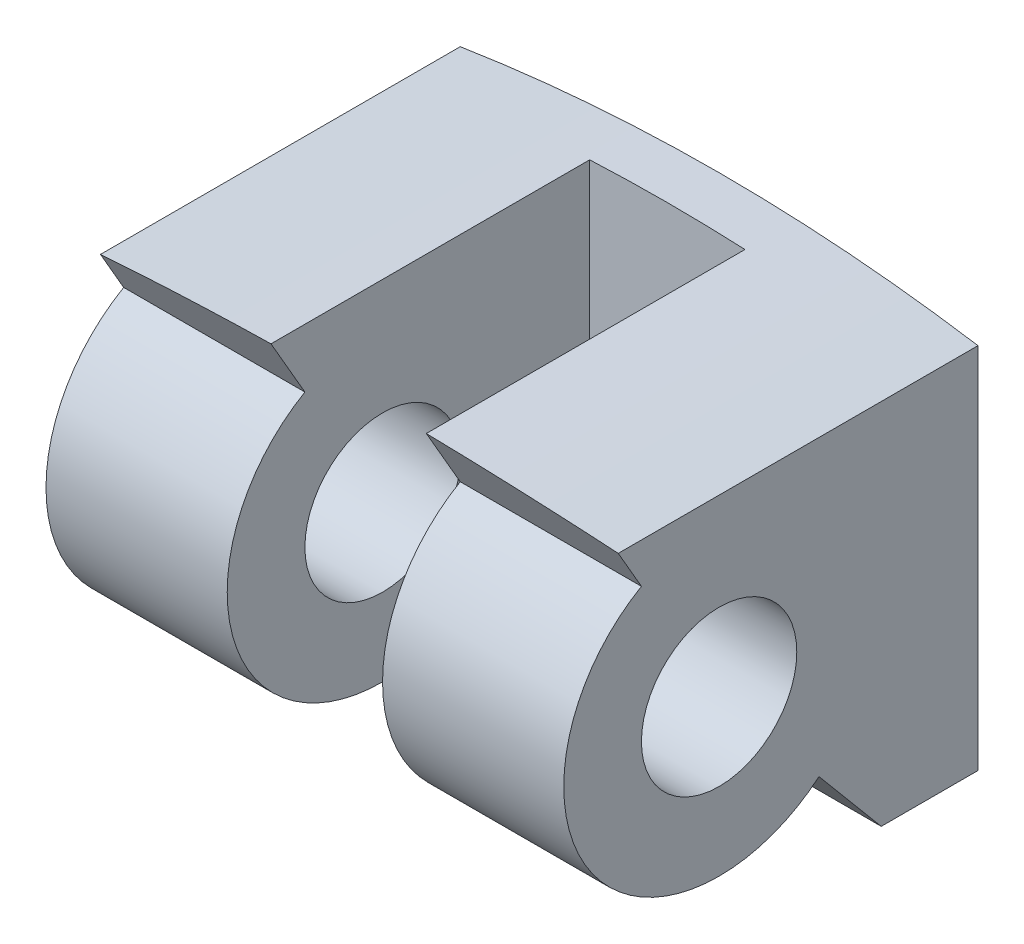
SolidWorks part; units mm, degrees
ref_plane "Alzado" through (0, 0, 0) normal (0, 0, 1) x (1, 0, 0)
ref_plane "Planta" through (0, 0, 0) normal (0, 1, 0) x (1, 0, 0)
ref_plane "Vista lateral" through (0, 0, 0) normal (1, 0, 0) x (0, 0, -1)
sketch "Croquis1" plane through (0, 0, 0) normal (0, 0, 1) x (1, 0, 0)
  line L2 (-5, 31.607) -> (-5, 24.5)
  line L3 (-5, 24.5) -> (5, 24.5)
  line L4 (5, 31.607) -> (5, 24.5)
  circle A0 centre (0, 0) radius 32 construction
  arc A1 (-5, 31.607) -> (5, 31.607) centre (0, 0) cw
  point P11 (0, 32)
  dimension "D1" = 64
  dimension "D2" = 7.5
  dimension "D3" = 10
extrude "Saliente-Extruir1" add sketch "Croquis1" along normal blind 8
sketch "Croquis2" plane through (0, 24.5, 0) normal (0, -1, 0) x (1, 0, 0)
  line L0 (0, 0) -> (0, 8) construction
  line L1 (-5, 0) -> (5, 0) construction
  line L2 (-5, 8) -> (5, 8) construction
  line L4 (1.5, 1) -> (-1.5, 1)
  line L5 (1.5, 1) -> (1.5, 8)
  line L6 (1.5, 8) -> (-1.5, 8)
  line L7 (-1.5, 1) -> (-1.5, 8)
  line L8 (1.5, 1) -> (-1.5, 8) construction
  line L9 (1.5, 8) -> (-1.5, 1) construction
  point P6 (0, 4.5)
  dimension "D1" = 1
  dimension "D2" = 3
extrude "Cortar-Extruir1" cut sketch "Croquis2" against normal blind 10
sketch "Croquis3" plane through (-1.5, 0, 0) normal (1, 0, 0) x (0, 0, -1)
  line L0 (-8, 28.2324) -> (-1, 28.2324) construction
  line L4 (-8, 31.9648) -> (-8, 24.5)
  line L5 (-8, 24.5) -> (-1, 24.5)
  line L6 (-1, 24.5) -> (-1, 31.9648)
  line L7 (-1, 31.9648) -> (-8, 31.9648)
  line L8 (-8, 31.9648) -> (-8, 24.5)
  line L9 (-8, 24.5) -> (-1, 24.5)
  line L10 (-1, 24.5) -> (-1, 31.9648)
  line L11 (-1, 31.9648) -> (-8, 31.9648)
  circle A0 centre (-5, 28.2324) radius 1.5
  point P8 (0, 0)
  dimension "D2" = 3
  dimension "D3" = 3
  dimension "D1" = 0
extrude "Cortar-Extruir3" cut sketch "Croquis3" against normal up to surface and the other way up to surface contours A0 | A0 region at (-1.5, 28.2324, 5) up to face at (-5, 28.0535, 4) other way up to face at (5, 28.0535, 4)
ref_axis "Eje1" through (1.5, 28.2324, 5) along (1, 0, 0)
ref_plane "Plano1" through (0, 28.2324, 0) normal (0, 1, 0) x (1, 0, 0)
sketch "Croquis6" plane through (0, 28.2324, 0) normal (0, 1, 0) x (1, 0, 0)
  line L1 (5, -6.5) -> (5, -3.5) construction
  line L15 (-5, -31.1268) -> (-5, -24.1278)
  line L16 (5, -6.5) -> (5, -3.5)
  line L17 (-5, -8) -> (-5, 0) construction
  line L18 (-5, -8) -> (-5, 0)
  line L20 (5, -5) -> (-5, -5)
  line L21 (5, -5) -> (5, -8)
  line L22 (5, -8) -> (-5, -8)
  line L23 (-5, -5) -> (-5, -8)
  line L24 (-5, -8) -> (5, -8)
  line L25 (-5, -8) -> (-5, -15)
  line L26 (-5, -15) -> (5, -15)
  line L27 (5, -8) -> (5, -15)
  dimension "D1" = 3
  dimension "D2" = 10
revolve "Cortar-Revolución4" cut sketch "Croquis6" angle 130 about axis through (1.5, 28.2324, 5) along (1, 0, 0) region at (0, 28.2324, 11.5) other way angle 60
